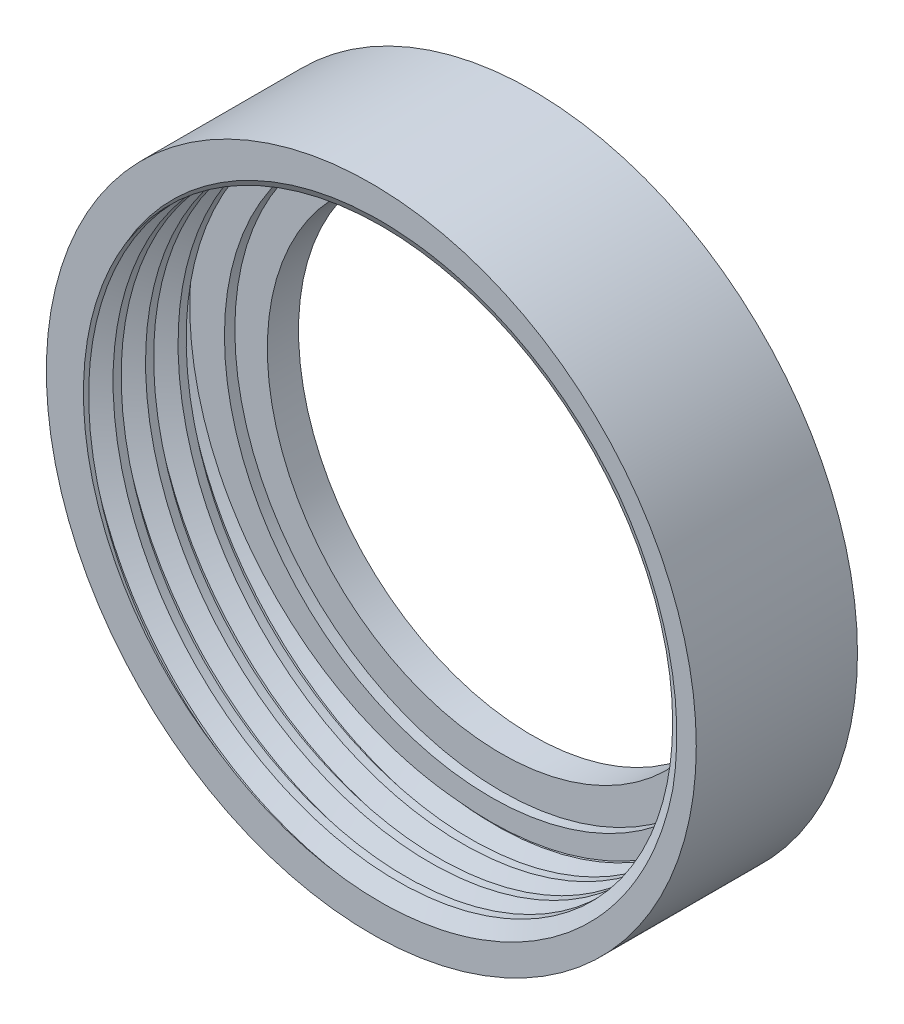
SolidWorks part; units mm, degrees
ref_plane "前视基准面" through (0, 0, 0) normal (0, 0, 1) x (1, 0, 0)
ref_plane "上视基准面" through (0, 0, 0) normal (0, 1, 0) x (1, 0, 0)
ref_plane "右视基准面" through (0, 0, 0) normal (1, 0, 0) x (0, 0, -1)
other "Configuration Table"
sketch "草图2" plane through (0, 0, 0) normal (0, 0, 1) x (1, 0, 0)
  circle A0 centre (0, 0) radius 9
  circle A1 centre (0, 0) radius 12.5
  dimension "D1" = 18
  dimension "D2" = 25
extrude "凸台-拉伸1" add sketch "草图2" along normal blind 1.2
sketch "草图3" plane through (0, 0, 1.2) normal (0, 0, 1) x (1, 0, 0)
  circle A0 centre (0, 0) radius 11.75
  circle A1 centre (0, 0) radius 12.5 construction
  circle A2 centre (0, 0) radius 12.5
  dimension "D1" = 23.5
extrude "凸台-拉伸2" add sketch "草图3" along normal blind 5
sketch "草图4" plane through (0, 0, 1.2) normal (0, 0, 1) x (1, 0, 0)
  circle A0 centre (0, 0) radius 10.25
  circle A1 centre (0, 0) radius 11.75 construction
  circle A2 centre (0, 0) radius 11.75
  dimension "D1" = 20.5
extrude "凸台-拉伸3" add sketch "草图4" along normal blind 0.4
thread "螺纹线1" pitch 1.25 method extrude trim with start face yes trim with end face yes profile "螺纹线轮廓1" start angle 0, offset 3, length 0, pitch 1.25, diameter 23.5
ref_plane "基准面1" through (-11.75, 0, 9.2) normal (0, -1, 0) x (-1, 0, 0)
sketch "螺纹线轮廓1" plane through (-11.75, 0, 9.2) normal (0, -1, 0) x (-1, 0, 0)
  line L0 (0, 0) -> (0, 1.25) construction
  line L11 (0, 0) -> (0, 1.0937)
  line L12 (0, 1.0937) -> (-0.6766, 0.7031)
  line L13 (-0.6766, 0.7031) -> (-0.6766, 0.3906)
  line L15 (-0.6766, 0.3906) -> (0, 0)
  line L17 (-0.6766, 0.5469) -> (0, 0.5469) construction
  point P2 (0, 0)
  dimension "Pitch" = 1.25
  dimension "Profile_Angle" = 60
  dimension "Profile_Land" = 0.3125
  dimension "Profile_Height" = 0.6766
